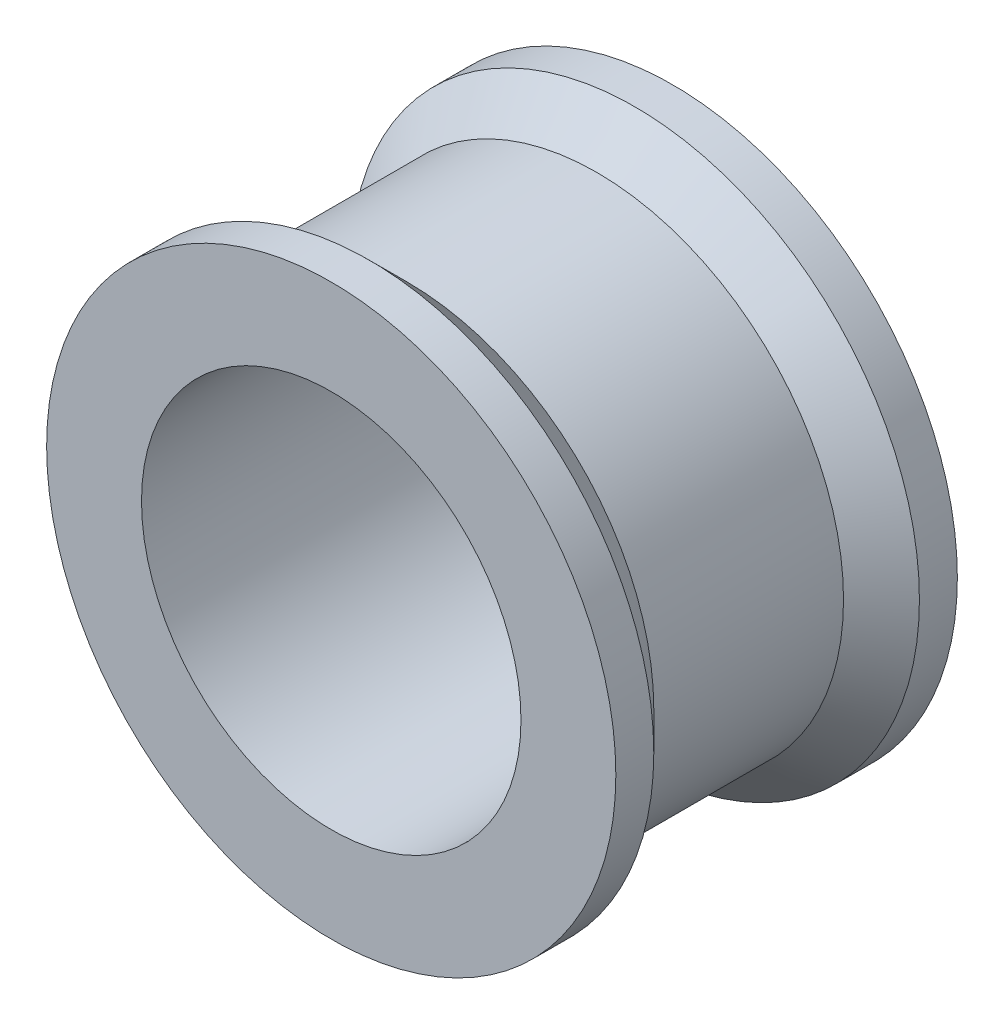
SolidWorks part; units mm, degrees
ref_plane "Front Plane" through (0, 0, 0) normal (0, 0, 1) x (1, 0, 0)
ref_plane "Top Plane" through (0, 0, 0) normal (0, 1, 0) x (1, 0, 0)
ref_plane "Right Plane" through (0, 0, 0) normal (1, 0, 0) x (0, 0, -1)
sketch "Sketch1" plane through (0, 0, 0) normal (0, 0, 1) x (1, 0, 0)
  circle A0 centre (0, 0) radius 5
  circle A1 centre (0, 0) radius 7.5
  dimension "D1" = 10
  dimension "D2" = 15
extrude "Boss-Extrude1" add sketch "Sketch1" along normal blind 1
sketch "Sketch2" plane through (0, 0, 1) normal (0, 0, 1) x (1, 0, 0)
  circle A0 centre (0, 0) radius 5
  circle A1 centre (0, 0) radius 6.5
  circle A2 centre (0, 0) radius 5 construction
  dimension "D1" = 13
extrude "Boss-Extrude2" add sketch "Sketch2" along normal blind 3.5
chamfer "Chamfer1" distance 1 angle 45 1 edges at (6.5, 0, 1)
mirror "Mirror5" about plane through (0, 0, 4.5) normal (0, 0, 1) of bodies 102
